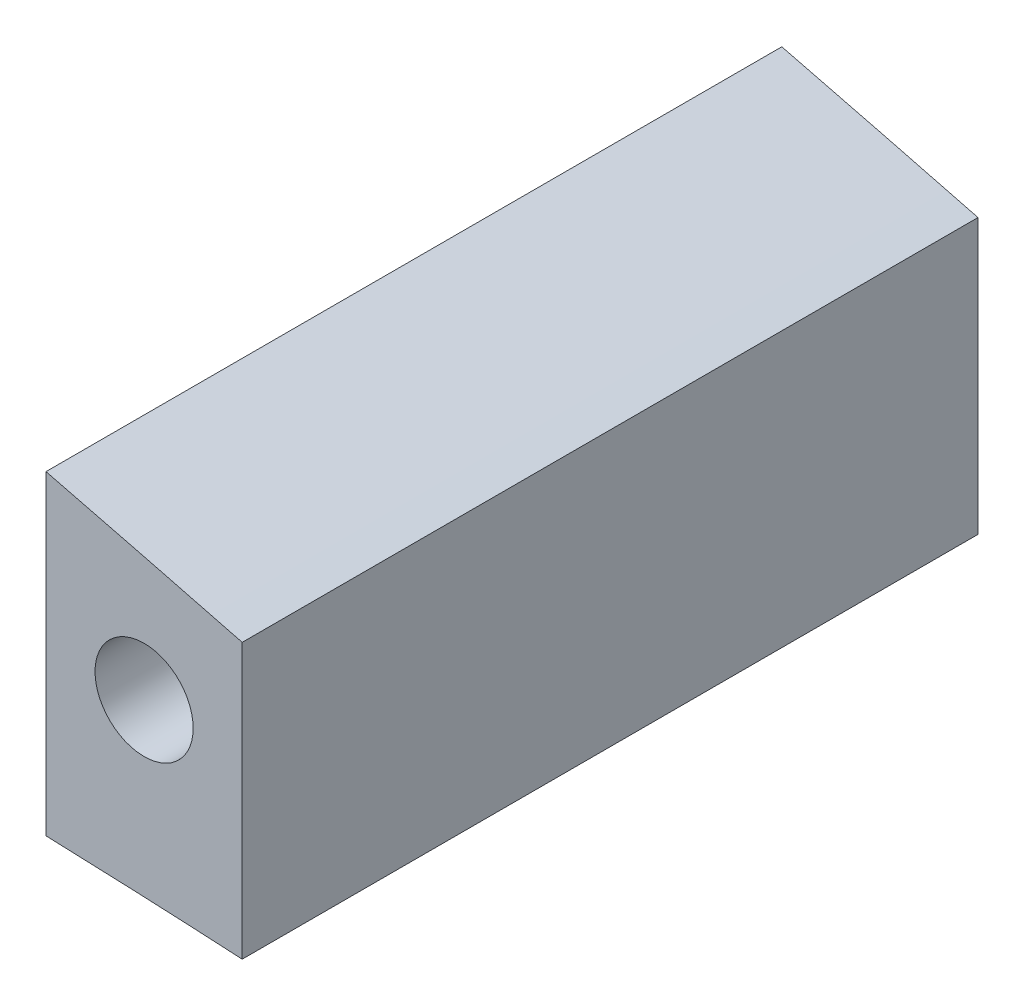
SolidWorks part; units mm, degrees
ref_plane "Front Plane" through (0, 0, 0) normal (0, 0, 1) x (1, 0, 0)
ref_plane "Top Plane" through (0, 0, 0) normal (0, 1, 0) x (1, 0, 0)
ref_plane "Right Plane" through (0, 0, 0) normal (1, 0, 0) x (0, 0, -1)
sketch "Sketch1" plane through (0, 0, 0) normal (0, 0, 1) x (1, 0, 0)
  spline S0 degree 3 poles (0.0006, 0.0001) (0.8106, 7.3592) (8.6491, 17.8566) (26.2867, 29.9752) (52.1111, 42.0692) (89.5976, 49.2908) (131.4008, 47.8848) (173.2567, 40.0411) (217.9611, 29.613) (256.9521, 19.5289) (290.3598, 8.711) (301.2732, 4.3828) (314.8169, -0.5162) (309.8463, 0.0001) knots 0 0 0 0 0.060864 0.113688 0.188609 0.312909 0.448482 0.557612 0.691544 0.852438 0.929756 0.976058 1 1 1 1
  spline S1 degree 3 poles (309.8463, 0.0001) (303.9568, 1.471) (293.9895, 2.094) (276.264, 4.5144) (260.8463, 5.4274) (235.8588, 7.8703) (205.1014, 8.8381) (157.7186, 9.0307) (110.4973, 6.1815) (66.5062, -0.5867) (36.4547, -6.0985) (15.3166, -6.1891) (1.2307, -6.9241) (0.0006, 0.0001) knots 0 0 0 0 0.057787 0.095275 0.171021 0.205339 0.335319 0.464904 0.658702 0.785512 0.893517 0.943092 1 1 1 1
extrude "Boss-Extrude1" add sketch "Sketch1" along normal blind 47.625
sketch "Sketch2" plane through (0, 0, 47.625) normal (0, 0, 1) x (1, 0, 0)
  circle A0 centre (20.32, 10.16) radius 6.35
  circle A1 centre (227.2963, 19.0501) radius 3.175
  dimension "D2" = 12.7
  dimension "D3" = 6.35
  dimension "D6" = 20.32
  dimension "D1" = 82.55
  dimension "D4" = 19.05
  dimension "D5" = 10.16
extrude "Cut-Extrude1" cut sketch "Sketch2" against normal through all
sketch "Sketch3" plane through (0, 0, 47.625) normal (0, 0, 1) x (1, 0, 0)
  line L1 (350.4863, -6.3499) -> (233.6463, -6.3499)
  line L2 (350.4863, -6.3499) -> (350.4863, 44.4501)
  line L3 (350.4863, 44.4501) -> (233.6463, 44.4501)
  line L4 (233.6463, -6.3499) -> (233.6463, 44.4501)
  circle A0 centre (227.2963, 19.0501) radius 3.175 construction
  dimension "D1" = 6.35
  dimension "D2" = 116.84
  dimension "D3" = 50.8
  dimension "D4" = 44.45
extrude "Cut-Extrude2" cut sketch "Sketch3" against normal through all contours L3 L4 L1 L2
sketch "Sketch4" plane through (0, 0, 47.625) normal (0, 0, 1) x (1, 0, 0)
  line L0 (233.6463, 7.6905) -> (233.6463, 25.4528) construction
  line L1 (220.9463, -24.2166) -> (-29.2042, -24.2166)
  line L2 (220.9463, -24.2166) -> (220.9463, 93.2727)
  line L3 (220.9463, 93.2727) -> (-29.2042, 93.2727)
  line L4 (-29.2042, -24.2166) -> (-29.2042, 93.2727)
  dimension "D1" = 12.7
extrude "Cut-Extrude3" cut sketch "Sketch4" against normal through all
